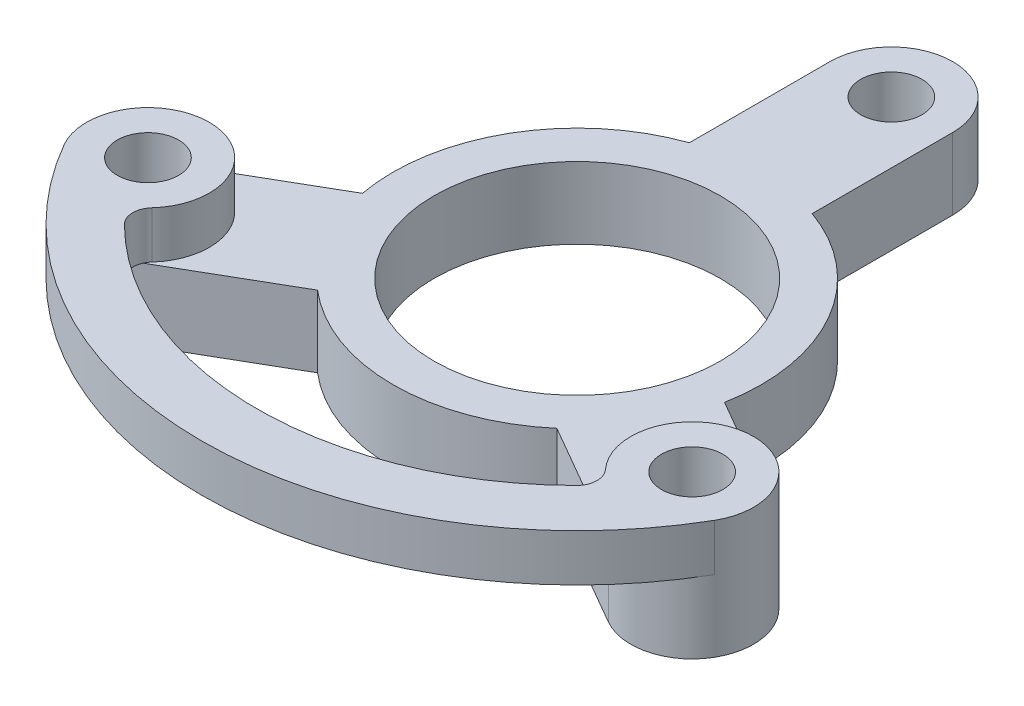
SolidWorks part; units mm, degrees
ref_plane "Front" through (0, 0, 0) normal (0, 0, 1) x (1, 0, 0)
ref_plane "Top" through (0, 0, 0) normal (0, 1, 0) x (1, 0, 0)
ref_plane "Right" through (0, 0, 0) normal (1, 0, 0) x (0, 0, -1)
sketch "Sketch1" plane through (0, 0, 0) normal (0, 1, 0) x (1, 0, 0)
  line L0 (0, 15.3575) -> (-13.3, -7.6788) construction
  line L1 (-13.3, -7.6788) -> (13.3, -7.6788) construction
  line L2 (13.3, -7.6788) -> (0, 15.3575) construction
  line L3 (-3, 8.4853) -> (-3, 15.3575)
  line L4 (3, 8.4853) -> (3, 15.3575)
  line L5 (8.8485, -1.6446) -> (14.8, -5.0807)
  line L6 (5.8485, -6.8407) -> (11.8, -10.2768)
  line L7 (-5.8485, -6.8407) -> (-11.8, -10.2768)
  line L8 (-8.8485, -1.6446) -> (-14.8, -5.0807)
  circle A0 centre (0, 0) radius 9
  circle A1 centre (0, 0) radius 15.3575 construction
  circle A2 centre (0, 15.3575) radius 3
  circle A3 centre (-13.3, -7.6788) radius 3
  circle A4 centre (13.3, -7.6788) radius 3
  circle A5 centre (0, 0) radius 7
  circle A6 centre (0, 15.3575) radius 1.5
  circle A7 centre (13.3, -7.6788) radius 1.5
  circle A8 centre (-13.3, -7.6788) radius 1.5
  point P25 (0, 0)
  dimension "D1" = 18
  dimension "D2" = 6
  dimension "D5" = 14
  dimension "D6" = 3
  dimension "D3" = 26.6
  dimension "D4" = 3
extrude "Boss-Extrude1" add sketch "Sketch1" along normal blind 3.5 contours A0 A5 | A2 L3 A0 L4 | A2 A6 | A3 L7 A0 L8 | A3 A8 | A4 L5 A0 L6 | A4 A7
sketch "Sketch2" plane through (0, 3.5, 0) normal (0, 1, 0) x (1, 0, 0)
  line L0 (-13.3, -7.6788) -> (-15.8981, -9.1788) construction
  line L1 (-13.3, -7.6788) -> (-10.7019, -6.1788) construction
  line L2 (-17.3629, -5.9605) -> (-11.688, -4.0124) construction
  line L3 (17.3629, -5.9605) -> (11.688, -4.0124) construction
  arc A0 (-15.8981, -9.1788) -> (15.8981, -9.1788) centre (0, 0) ccw
  arc A1 (-14.8, -5.0807) -> (-11.8, -10.2768) centre (-13.3, -7.6788) ccw construction
  arc A2 (-14.8, -5.0807) -> (-11.8, -10.2768) centre (-13.3, -7.6788) ccw
  arc A3 (-10.7019, -6.1788) -> (10.7019, -6.1788) centre (0, 0) ccw
  arc A4 (11.8, -10.2768) -> (14.8, -5.0807) centre (13.3, -7.6788) ccw construction
  arc A5 (11.8, -10.2768) -> (14.8, -5.0807) centre (13.3, -7.6788) ccw
  arc A6 (17.3629, -5.9605) -> (-17.3629, -5.9605) centre (0, 0) ccw construction
  arc A7 (11.688, -4.0124) -> (-11.688, -4.0124) centre (0, 0) ccw construction
  arc A8 (11.8, -10.2768) -> (-11.8, -10.2768) centre (0, 0) cw
  circle A9 centre (13.3, -7.6788) radius 3
  circle A10 centre (-13.3, -7.6788) radius 3
  arc A11 (-11.688, -4.0124) -> (-10.7019, -6.1788) centre (0, 0) ccw construction
  arc A12 (-17.3629, -5.9605) -> (-15.8981, -9.1788) centre (0, 0) ccw construction
  arc A13 (15.8981, -9.1788) -> (17.3629, -5.9605) centre (0, 0) ccw construction
  arc A14 (10.7019, -6.1788) -> (11.688, -4.0124) centre (0, 0) ccw construction
extrude "Boss-Extrude2" add sketch "Sketch2" along normal blind 2.3
fillet "Fillet2" radius 1 2 edges at (-11.8, 4.65, 10.2768) (11.8, 4.65, 10.2768)
